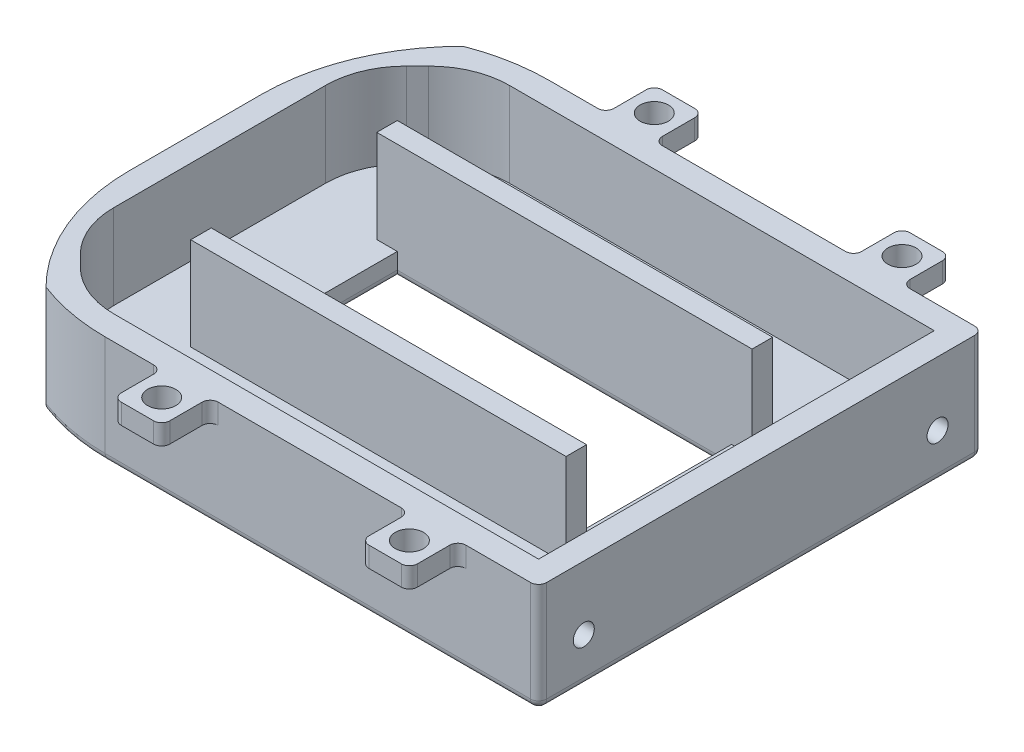
SolidWorks part; units mm, degrees
ref_plane "Front Plane" through (0, 0, 0) normal (0, 0, 1) x (1, 0, 0)
ref_plane "Top Plane" through (0, 0, 0) normal (0, 1, 0) x (1, 0, 0)
ref_plane "Right Plane" through (0, 0, 0) normal (1, 0, 0) x (0, 0, -1)
sketch "Sketch1" plane through (0, 0, 0) normal (0, 1, 0) x (1, 0, 0)
  line L0 (0, 46) -> (9, 55)
  line L1 (9, 0) -> (161, 0)
  line L2 (0, 9) -> (0, 46)
  line L3 (9, 55) -> (161, 55)
  line L4 (170, 9) -> (170, 46)
  line L5 (0, 9) -> (9, 0)
  line L6 (161, 55) -> (170, 46)
  line L7 (161, 0) -> (170, 9)
  point P0 (0, 0)
  point P1 (170, 55)
  point P2 (0, 55)
  point P3 (170, 0)
  dimension "D1" = 55
  dimension "D2" = 170
extrude "Boss-Extrude1" add sketch "Sketch1" along normal blind 30
sketch "Sketch2" plane through (0, 30, 0) normal (0, 1, 0) x (1, 0, 0)
  line L8 (3, 44.7574) -> (3, 10.2426)
  line L9 (10.2426, 3) -> (159.7574, 3)
  line L10 (167, 10.2426) -> (167, 44.7574)
  line L11 (159.7574, 52) -> (10.2426, 52)
  line L12 (3, 44.7574) -> (3, 10.2426)
  line L13 (10.2426, 3) -> (159.7574, 3)
  line L14 (167, 10.2426) -> (167, 44.7574)
  line L15 (159.7574, 52) -> (10.2426, 52)
  line L20 (3, 10.2426) -> (10.2426, 3)
  line L21 (3, 10.2426) -> (10.2426, 3)
  line L22 (159.7574, 3) -> (167, 10.2426)
  line L23 (159.7574, 3) -> (167, 10.2426)
  line L24 (167, 44.7574) -> (159.7574, 52)
  line L25 (167, 44.7574) -> (159.7574, 52)
  line L26 (10.2426, 52) -> (3, 44.7574)
  line L27 (10.2426, 52) -> (3, 44.7574)
  dimension "D1" = 3
shell "Shell2" thickness 3
extrude "Cut-Extrude2" cut sketch "Sketch2" against normal up to next
sketch "Length from bottom to Gear/Pin connection" plane through (0, 0, 0) normal (0, -1, 0) x (1, 0, 0)
  line L0 (0, -27.5) -> (25, -27.5) construction
  line L1 (0, -19.8) -> (0, 19.8) construction
  circle A0 centre (25, -27.5) radius 6.9102
  dimension "D1" = 25
sketch "Sketch4" plane through (0, 0, 0) normal (0, -1, 0) x (1, 0, 0)
  circle A0 centre (25, -27.5) radius 3.8
  dimension "D1" = 7.6
sketch "Outline of actual motor" plane through (0, 3, 0) normal (0, 1, 0) x (1, 0, 0)
  line L0 (15, 37.5) -> (55.9, 37.5) construction
  line L1 (55.9, 37.5) -> (55.9, 17.5) construction
  line L2 (55.9, 17.5) -> (15, 17.5) construction
  line L3 (15, 17.5) -> (15, 37.5) construction
  line L4 (55.2, 37.5) -> (15.7, 37.5) construction
  line L5 (15.7, 17.5) -> (55.2, 17.5) construction
  line L6 (55.9, 18.2) -> (55.9, 36.8) construction
  line L7 (15, 36.8) -> (15, 18.2) construction
  dimension "D1" = 0
  dimension "D2" = 0
  dimension "D3" = 0
  dimension "D4" = 0
sketch "Outline of motor press fit" plane through (0, 3, 0) normal (0, 1, 0) x (1, 0, 0)
  line L8 (15, 37.5) -> (55.9, 37.5) construction
  line L9 (14.75, 17.25) -> (56.15, 17.25)
  line L10 (14.75, 17.25) -> (14.75, 37.75)
  line L11 (14.75, 37.75) -> (56.15, 37.75)
  line L12 (56.15, 17.25) -> (56.15, 37.75)
  line L13 (55.9, 37.5) -> (55.9, 17.5) construction
  line L14 (55.9, 17.5) -> (15, 17.5) construction
  line L15 (15, 17.5) -> (15, 37.5) construction
  dimension "D1" = 0.25
  dimension "D2" = 0.25
  dimension "D3" = 0.25
  dimension "D4" = 0.25
sketch "Sketch16" plane through (0, 3, 0) normal (0, 1, 0) x (1, 0, 0)
  line L0 (18.21, 40.29) -> (52.69, 40.29)
  line L1 (52.69, 37.75) -> (18.21, 37.75)
  line L2 (18.21, 17.25) -> (52.69, 17.25)
  line L3 (52.69, 14.71) -> (18.21, 14.71)
  line L4 (14.75, 37.75) -> (12.21, 37.75)
  line L5 (12.21, 37.75) -> (58.69, 37.75)
  line L6 (58.69, 17.25) -> (56.15, 17.25)
  line L7 (12.21, 17.25) -> (14.75, 17.25)
  line L8 (12.21, 40.29) -> (18.21, 40.29) construction
  line L9 (12.21, 40.29) -> (12.21, 37.75) construction
  line L12 (12.21, 14.71) -> (58.69, 14.71)
  line L13 (58.69, 14.71) -> (58.69, 40.29)
  line L14 (58.69, 40.29) -> (12.21, 40.29)
  line L15 (12.21, 40.29) -> (12.21, 14.71)
  line L16 (12.21, 14.71) -> (18.21, 14.71)
  line L17 (58.69, 14.71) -> (58.69, 17.25)
  line L18 (58.69, 40.29) -> (52.69, 40.29)
  line L19 (12.21, 40.29) -> (12.21, 37.75)
  line L21 (14.75, 37.75) -> (56.15, 37.75) construction
  line L22 (18.21, 37.75) -> (14.75, 37.75)
  line L24 (35.45, 40.29) -> (35.45, 14.71) construction
  line L25 (12.21, 27.5) -> (58.69, 27.5) construction
  line L26 (18.21, 40.29) -> (12.21, 40.29)
  line L27 (12.21, 17.25) -> (12.21, 14.71)
  line L29 (58.69, 40.29) -> (58.69, 37.75)
  line L31 (52.69, 37.75) -> (56.15, 37.75)
  line L33 (52.69, 40.29) -> (58.69, 40.29)
  line L34 (52.69, 14.71) -> (58.69, 14.71)
  line L36 (52.69, 17.25) -> (56.15, 17.25)
  line L39 (58.69, 14.71) -> (58.69, 17.25)
  line L40 (18.21, 14.71) -> (12.21, 14.71)
  line L42 (18.21, 17.25) -> (14.75, 17.25)
  line L45 (12.21, 14.71) -> (12.21, 17.25)
  line L46 (58.69, 37.75) -> (58.69, 40.29)
  line L47 (52.69, 14.71) -> (58.69, 14.71)
  dimension "D2" = 6
  dimension "D1" = 2.54
extrude "Boss-Extrude5" add sketch "Sketch16" along normal blind 25.5 contours L29 L18 L0 L26 L19 L4 L5 L1 | L2 L42 L7 L27 L16 L3 L34 L17 L6 L36
sketch "Sketch17" plane through (0, 28.5, 0) normal (0, 1, 0) x (1, 0, 0)
  line L0 (58.69, 40.29) -> (12.21, 40.29) construction
  line L1 (56.193, 40.29) -> (64.193, 40.29)
  line L2 (56.193, 40.29) -> (56.193, 14.71)
  line L3 (56.193, 14.71) -> (64.193, 14.71)
  line L4 (64.193, 40.29) -> (64.193, 14.71)
  line L5 (14.75, 37.75) -> (14.75, 40.29) construction
  line L6 (58.69, 40.29) -> (12.21, 40.29) construction
  line L8 (14.75, 40.29) -> (6.75, 40.29)
  line L9 (14.75, 40.29) -> (14.75, 14.71)
  line L10 (14.75, 14.71) -> (6.75, 14.71)
  line L11 (6.75, 40.29) -> (6.75, 14.71)
  dimension "D1" = 8
  dimension "D2" = 8
extrude "Boss-Extrude6" add sketch "Sketch17" against normal blind 5
sketch "Sketch18" plane through (0, 28.5, 0) normal (0, 1, 0) x (1, 0, 0)
  circle A0 centre (59.75, 32.5) radius 1.75
  circle A1 centre (59.75, 22.5) radius 1.75
  circle A2 centre (11.15, 22.5) radius 1.75
  circle A3 centre (11.15, 32.5) radius 1.75
  dimension "D1" = 3.5
  dimension "D2" = 3.5
  dimension "D3" = 3.5
  dimension "D4" = 3.5
extrude "Cut-Extrude3" cut sketch "Sketch18" against normal up to next
sketch "Sketch20" plane through (0, 30, 0) normal (0, 1, 0) x (1, 0, 0)
  line L1 (-8.4121, 65.847) -> (189.0699, 65.847)
  line L2 (-8.4121, 65.847) -> (-8.4121, -17.3253)
  line L3 (-8.4121, -17.3253) -> (189.0699, -17.3253)
  line L4 (189.0699, 65.847) -> (189.0699, -17.3253)
extrude "Cut-Extrude4" cut sketch "Sketch20" against normal offset from surface (16.5 mm away) 13.5 up to face at (85, 0, -27.5)
sketch "Sketch21" plane through (0, 0, 0) normal (0, 0, 1) x (1, 0, 0)
  line L0 (80.8737, 0) -> (80.8737, 13.5) construction
  line L1 (30.25, 0) -> (-30.25, 0) construction
  dimension "D1" = 13.5
extrude "Cut-Extrude5" cut sketch "Outline of motor press fit" against normal up to next
sketch "Sketch24" plane through (0, 13.5, 0) normal (0, 1, 0) x (1, 0, 0)
  line L1 (12.21, 40.29) -> (58.69, 40.29)
  line L2 (12.21, 40.29) -> (12.21, 37.75)
  line L3 (12.21, 37.75) -> (58.69, 37.75)
  line L4 (58.69, 40.29) -> (58.69, 37.75)
  line L5 (12.21, 17.25) -> (58.69, 17.25)
  line L6 (12.21, 17.25) -> (12.21, 14.71)
  line L7 (12.21, 14.71) -> (58.69, 14.71)
  line L8 (58.69, 17.25) -> (58.69, 14.71)
extrude "Boss-Extrude7" add sketch "Sketch24" along normal blind 1
sketch "Sketch25" plane through (0, 0, 0) normal (0, -1, 0) x (1, 0, 0)
  line L0 (0, -27.5) -> (70, -27.5) construction
  line L1 (70, 13.4618) -> (70, -84.299)
  line L2 (70, -84.299) -> (188.2354, -84.299)
  line L3 (188.2354, -84.299) -> (188.2354, 23.0423)
  line L4 (188.2354, 23.0423) -> (70, 19.7184)
  line L5 (70, 19.7184) -> (70, 13.4618)
  dimension "D1" = 70
extrude "Cut-Extrude6" cut sketch "Sketch25" against normal through all both and the other way through all
sketch "Sketch26" plane through (70, 0, 0) normal (1, 0, 0) x (0, 0, -1)
  line L1 (55, 13.5) -> (0, 13.5)
  line L2 (55, 13.5) -> (55, 0)
  line L3 (55, 0) -> (0, 0)
  line L4 (0, 13.5) -> (0, 0)
extrude "Boss-Extrude8" add sketch "Sketch26" against normal blind 3
fillet "Fillet1" radius 25 2 edges at (0, 6.75, -9) (0, 6.75, -46)
fillet "Fillet2" radius 25 2 edges at (9, 6.75, 0) (9, 6.75, -55)
sketch "Sketch28" plane through (0, 13.5, 0) normal (0, 1, 0) x (1, 0, 0)
  line L0 (70, 55) -> (60, 55) construction
  line L1 (16.3262, 55) -> (70, 55) construction
  line L2 (16.3262, 55) -> (23.3262, 55)
  line L3 (23.3262, 55) -> (29.3262, 61) construction
  line L4 (23.3262, 55) -> (29.3262, 55)
  line L5 (23.3262, 55) -> (23.3262, 61)
  line L6 (23.3262, 61) -> (29.3262, 61)
  line L7 (29.3262, 55) -> (29.3262, 61)
  line L8 (60, 55) -> (54, 55)
  line L9 (60, 55) -> (60, 61)
  line L10 (60, 61) -> (54, 61)
  line L11 (54, 55) -> (54, 61)
  line L12 (54, 55) -> (60, 61) construction
  line L13 (3, 27.5) -> (67, 27.5) construction
  line L14 (3, 10.2426) -> (3, 44.7574) construction
  line L15 (67, 3) -> (67, 52) construction
  line L16 (54, 0) -> (60, -6) construction
  line L17 (23.3262, 0) -> (29.3262, -6) construction
  line L18 (54, 0) -> (54, -6)
  line L19 (60, -6) -> (54, -6)
  line L20 (60, 0) -> (60, -6)
  line L21 (60, 0) -> (54, 0)
  line L22 (29.3262, 0) -> (29.3262, -6)
  line L23 (23.3262, -6) -> (29.3262, -6)
  line L24 (23.3262, 0) -> (23.3262, -6)
  line L25 (23.3262, 0) -> (29.3262, 0)
  circle A0 centre (26.3262, 58) radius 1.75
  circle A1 centre (57, 58) radius 1.75
  circle A2 centre (57, -3) radius 1.75
  circle A3 centre (26.3262, -3) radius 1.75
  line M15 (16.3262, 0) -> (70, 0)
  line M17 (70, 55) -> (16.3262, 55)
  dimension "D7" = 3.5
  dimension "D8" = 3.5
  dimension "D1" = 10
  dimension "D3" = 6
  dimension "D4" = 6
  dimension "D5" = 6
  dimension "D6" = 6
extrude "Boss-Extrude9" add sketch "Sketch28" against normal blind 2.5 contours L7 L6 L5 A0 M17 | L11 L9 L10 A1 M17 | L20 L18 L19 A2 M15 | L24 L23 L22 A3 M15
fillet "Fillet3" radius 1 30 edges at (35.45, 0, -37.75) (56.15, 0, -27.5) (35.45, 0, -17.25) (14.75, 0, -27.5) (60, 12.25, -55) (60, 12.25, -61) (54, 12.25, -61) (54, 12.25, -55) (29.3262, 12.25, -55) (29.3262, 12.25, -61) (23.3262, 12.25, -61) (23.3262, 12.25, -55) (23.3262, 12.25, 0) (23.3262, 12.25, 6) (29.3262, 12.25, 6) (29.3262, 12.25, 0) (54, 12.25, 0) (54, 12.25, 6) (60, 12.25, 6) (60, 12.25, 0) (70, 0, -27.5) (43.1631, 0, -55) (11.7468, 0, -54.577) (1.903, 0, -45.2117) (0, 0, -27.5) (1.903, 0, -9.7883) (11.7468, 0, -0.423) (43.1631, 0, 0) (70, 6.75, 0) (70, 6.75, -55)
fillet "Fillet4" radius 10 4 edges at (10.2426, 8.25, -52) (3, 8.25, -44.7574) (10.2426, 8.25, -3) (3, 8.25, -10.2426)
sketch "Sketch29" plane through (70, 0, 0) normal (1, 0, 0) x (0, 0, -1)
sketch "Sketch30" plane through (70, 0, 0) normal (1, 0, 0) x (0, 0, -1)
  line L0 (1, 1) -> (5.5962, 5.5962) construction
  line L1 (1, 1) -> (54, 1) construction
  line L2 (54, 1) -> (49.4038, 5.5962) construction
  line L3 (54, 1) -> (54, 13.5) construction
  circle A0 centre (5.5962, 5.5962) radius 1.3
  circle A1 centre (49.4038, 5.5962) radius 1.3
  dimension "D1" = 2.6
  dimension "D3" = 2.6
  dimension "D2" = 135
  dimension "D4" = 135
extrude "Cut-Extrude7" cut sketch "Sketch30" against normal up to next
equation "\"arm width\"=55"
equation "\"D1@Sketch1\"=\"arm width\""
equation "\"arm length\"=170"
equation "\"D2@Sketch1\"=\"arm length\""
equation "\"screwHoleDiameterMG996R\"= 3.5"
equation "\"D1@Sketch18\"=\"screwHoleDiameterMG996R\""
equation "\"D2@Sketch18\"=\"screwHoleDiameterMG996R\""
equation "\"D3@Sketch18\"=\"screwHoleDiameterMG996R\""
equation "\"D1@Sketch28\"=10"
equation "\"D2@Sketch28\"=7"
equation "\"D3@Sketch28\"=6"
equation "\"D4@Sketch28\"=6"
equation "\"D5@Sketch28\"=6"
equation "\"D6@Sketch28\"=6"
equation "\"D7@Sketch28\"=\"screwHoleDiameterMG996R\""
equation "\"D8@Sketch28\"=\"screwHoleDiameterMG996R\""
